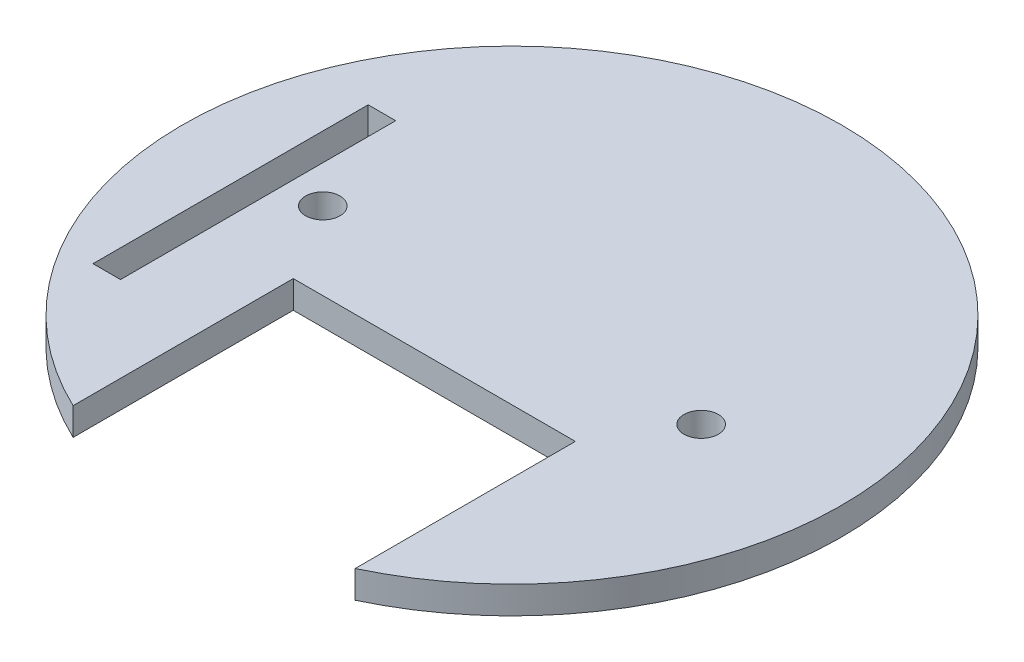
SolidWorks part; units mm, degrees
ref_plane "Front Plane" through (0, 0, 0) normal (0, 0, 1) x (1, 0, 0)
ref_plane "Top Plane" through (0, 0, 0) normal (0, 1, 0) x (1, 0, 0)
ref_plane "Right Plane" through (0, 0, 0) normal (1, 0, 0) x (0, 0, -1)
sketch "Sketch1" plane through (0, 0, 0) normal (0, 1, 0) x (1, 0, 0)
  line L0 (-47.9, 0) -> (47.9, 0) construction
  line L1 (0, 47.9) -> (0, -47.75) construction
  line L2 (-20.5, -43.2916) -> (-20.5, -11.2916)
  line L3 (-20.5, -11.2916) -> (20.5, -11.2916)
  line L4 (20.5, -11.2916) -> (20.5, -43.2916)
  line L6 (-32.9281, -23.9749) -> (-36.9281, -23.9749)
  line L7 (-32.9281, -23.9749) -> (-32.9281, 16.0251)
  line L8 (-32.9281, 16.0251) -> (-36.9281, 16.0251)
  line L9 (-36.9281, -23.9749) -> (-36.9281, 16.0251)
  arc A0 (20.5, -43.2916) -> (-20.5, -43.2916) centre (0, 0) ccw
  circle A1 centre (-27.5, 0) radius 2.5
  circle A2 centre (27.5, 0) radius 2.5
  dimension "D1" = 95.8
  dimension "D2" = 5
  dimension "D3" = 55
  dimension "D4" = 32
  dimension "D5" = 41
  dimension "D6" = 40
  dimension "D7" = 4
extrude "Boss-Extrude2" add sketch "Sketch1" along normal blind 4
